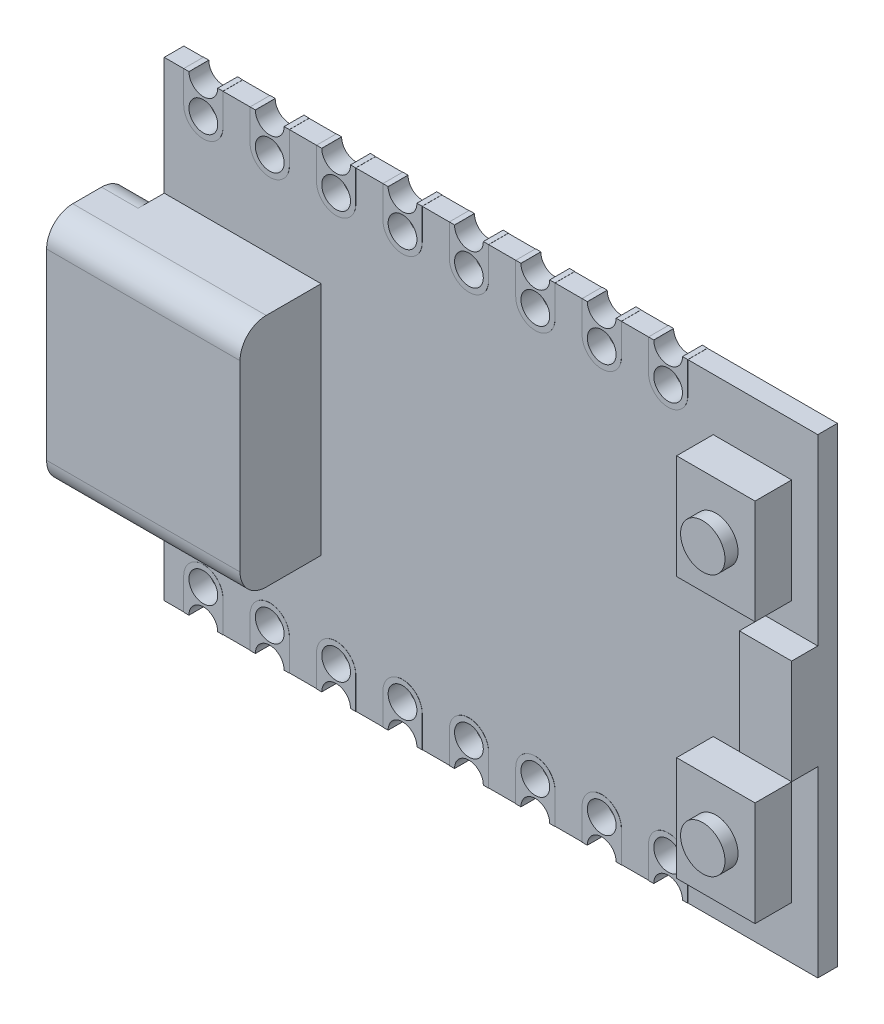
SolidWorks part; units mm, degrees
ref_plane "Plano frontal" through (0, 0, 0) normal (0, 0, 1) x (1, 0, 0)
ref_plane "Plano superior" through (0, 0, 0) normal (0, 1, 0) x (1, 0, 0)
ref_plane "Plano direito" through (0, 0, 0) normal (1, 0, 0) x (0, 0, -1)
sketch "Esboço1" plane through (0, 0, 0) normal (0, 0, 1) x (1, 0, 0)
  line L1 (-25, 18) -> (0, 18)
  line L2 (-25, 18) -> (-25, 0)
  line L3 (-25, 0) -> (0, 0)
  line L4 (0, 18) -> (0, 0)
  dimension "D1" = 18
  dimension "D2" = 25
extrude "PCI" add sketch "Esboço1" along normal blind 0.75
sketch "Esboço2" plane through (0, 0, 0.75) normal (0, 0, 1) x (1, 0, 0)
  line L0 (-15.0711, 10.1145) -> (-11.5355, 13.65)
  line L1 (-15.0711, 10.1145) -> (-11.5355, 6.5789)
  line L2 (-11.5355, 13.65) -> (-8, 10.1145)
  line L3 (-11.5355, 6.5789) -> (-8, 10.1145)
  line L4 (0, 0) -> (0, 18) construction
  line L5 (0, 18) -> (-25, 18) construction
  point P8 (0, 0)
  point P9 (-11.4211, 10.1145)
  point P10 (-11.4211, 10.1145)
  dimension "D1" = 45
  dimension "D2" = 4.35
  dimension "D3" = 8
  dimension "D4" = 5
extrude "ESP32" add sketch "Esboço2" against normal blind 2
sketch "Esboço3" plane through (0, 0, 0.75) normal (0, 0, 1) x (1, 0, 0)
  line L0 (-25, 18) -> (-25, 0) construction
  line L1 (-19, 13.5) -> (-26.4, 13.5)
  line L2 (-19, 13.5) -> (-19, 4.5)
  line L3 (-19, 4.5) -> (-26.4, 4.5)
  line L4 (-26.4, 13.5) -> (-26.4, 4.5)
  line L5 (-25, 9) -> (0, 9) construction
  line L6 (0, 0) -> (0, 18) construction
  dimension "D1" = 1.4
  dimension "D2" = 7.4
  dimension "D3" = 4.5
  dimension "D4" = 9
extrude "USB-C" add sketch "Esboço3" along normal blind 3.1
fillet "Arredondamento inferior USB" radius 1 2 edges at (-25.7, 13.5, 0.75) (-25.7, 4.5, 0.75)
fillet "Arredondamento Superior USB" radius 1 2 edges at (-22.7, 13.5, 3.85) (-22.7, 4.5, 3.85)
sketch "Esboço8" plane through (-26.4, 0, 0) normal (-1, 0, 0) x (0, 0, 1)
  line L0 (1.05, 12.5) -> (1.05, 5.5)
  line L1 (1.75, 4.8) -> (2.85, 4.8)
  line L2 (3.55, 5.5) -> (3.55, 12.5)
  line L3 (2.85, 13.2) -> (1.75, 13.2)
  line L4 (2.85, 13.5) -> (1.75, 13.5) construction
  line L5 (3.85, 12.5) -> (3.85, 5.5) construction
  arc A0 (1.75, 13.2) -> (1.05, 12.5) centre (1.75, 12.5) ccw
  arc A1 (1.05, 5.5) -> (1.75, 4.8) centre (1.75, 5.5) ccw
  arc A2 (2.85, 4.8) -> (3.55, 5.5) centre (2.85, 5.5) ccw
  arc A3 (3.55, 12.5) -> (2.85, 13.2) centre (2.85, 12.5) ccw
  dimension "D1" = 0.7
  dimension "D2" = 0.3
  dimension "D3" = 2.8
  dimension "D4" = 0.3
  dimension "D5" = 8.7
extrude "Furo USB" cut sketch "Esboço8" against normal blind 3.1
sketch "Esboço9" plane through (-26.4, 0, 0) normal (-1, 0, 0) x (0, 0, 1)
  line L0 (2.3, 13.2) -> (2.3, 4.8) construction
  line L1 (2.85, 13.2) -> (1.75, 13.2) construction
  line L2 (1.75, 4.8) -> (2.85, 4.8) construction
  line L3 (1.925, 5.4) -> (2.675, 5.4)
  line L4 (1.925, 5.4) -> (1.925, 12.6)
  line L5 (1.925, 12.6) -> (2.675, 12.6)
  line L6 (2.675, 5.4) -> (2.675, 12.6)
  line L7 (1.925, 5.4) -> (2.675, 12.6) construction
  line L8 (1.925, 12.6) -> (2.675, 5.4) construction
  point P4 (2.3, 9)
  dimension "D1" = 0.6
  dimension "D2" = 0.6
  dimension "D3" = 0.75
extrude "ConexaoUSB" add sketch "Esboço9" against normal up to next from offset 0.5 offset against normal yes
sketch "Esboço10" plane through (0, 0, 0.75) normal (0, 0, 1) x (1, 0, 0)
  line L0 (-25, 0) -> (0, 0) construction
  line L1 (-25, 4.5) -> (-25, 0) construction
  line L2 (-23.5, 1.2) -> (-23.5, -0.7241) construction
  line L3 (-23.5, 16.8) -> (-23.5, 18.7241) construction
  line L4 (0, 9) -> (-28.3512, 9) construction
  line L5 (0, 0) -> (0, 18) construction
  circle A0 centre (-23.5, 1.2) radius 0.55
  circle A1 centre (-23.5, 0) radius 0.55
  circle A2 centre (-20.96, 1.2) radius 0.55
  circle A3 centre (-20.96, 0) radius 0.55
  circle A4 centre (-18.42, 1.2) radius 0.55
  circle A5 centre (-18.42, 0) radius 0.55
  circle A6 centre (-15.88, 1.2) radius 0.55
  circle A7 centre (-15.88, 0) radius 0.55
  circle A8 centre (-13.34, 1.2) radius 0.55
  circle A9 centre (-13.34, 0) radius 0.55
  circle A10 centre (-10.8, 1.2) radius 0.55
  circle A11 centre (-10.8, 0) radius 0.55
  circle A12 centre (-8.26, 1.2) radius 0.55
  circle A13 centre (-8.26, 0) radius 0.55
  circle A14 centre (-5.72, 1.2) radius 0.55
  circle A15 centre (-5.72, 0) radius 0.55
  circle A16 centre (-5.72, 18) radius 0.55
  circle A17 centre (-5.72, 16.8) radius 0.55
  circle A18 centre (-8.26, 18) radius 0.55
  circle A19 centre (-8.26, 16.8) radius 0.55
  circle A20 centre (-10.8, 18) radius 0.55
  circle A21 centre (-10.8, 16.8) radius 0.55
  circle A22 centre (-13.34, 18) radius 0.55
  circle A23 centre (-13.34, 16.8) radius 0.55
  circle A24 centre (-15.88, 18) radius 0.55
  circle A25 centre (-15.88, 16.8) radius 0.55
  circle A26 centre (-18.42, 18) radius 0.55
  circle A27 centre (-18.42, 16.8) radius 0.55
  circle A28 centre (-20.96, 18) radius 0.55
  circle A29 centre (-20.96, 16.8) radius 0.55
  circle A30 centre (-23.5, 18) radius 0.55
  circle A31 centre (-23.5, 16.8) radius 0.55
  dimension "D1" = 1.2
  dimension "D2" = 1.1
  dimension "D7" = 2.54
  dimension "D3" = 0
  dimension "D4" = 1.5
  dimension "D5" = 8
extrude "FurosPCB" cut sketch "Esboço10" against normal up to next (0.75 mm away)
sketch "Esboço11" plane through (0, 0, 0.75) normal (0, 0, 1) x (1, 0, 0)
  line L0 (-24.25, 1.2) -> (-24.25, 0)
  line L1 (-22.75, 1.2) -> (-22.75, 0)
  line L2 (-20.21, 1.2) -> (-20.21, 0)
  line L4 (-24.25, 0) -> (-24.05, 0)
  line L5 (-22.95, 0) -> (-22.75, 0)
  line L6 (-20.41, 0) -> (-20.21, 0)
  line L7 (-21.71, 1.2) -> (-21.71, 0)
  line L8 (-21.71, 0) -> (-21.51, 0)
  line L9 (-17.67, 1.2) -> (-17.67, 0)
  line L10 (-17.87, 0) -> (-17.67, 0)
  line L11 (-19.17, 1.2) -> (-19.17, 0)
  line L12 (-19.17, 0) -> (-18.97, 0)
  line L13 (-15.13, 1.2) -> (-15.13, 0)
  line L14 (-15.33, 0) -> (-15.13, 0)
  line L15 (-16.63, 1.2) -> (-16.63, 0)
  line L16 (-16.63, 0) -> (-16.43, 0)
  line L17 (-12.59, 1.2) -> (-12.59, 0)
  line L18 (-12.79, 0) -> (-12.59, 0)
  line L19 (-14.09, 1.2) -> (-14.09, 0)
  line L20 (-14.09, 0) -> (-13.89, 0)
  line L21 (-10.05, 1.2) -> (-10.05, 0)
  line L22 (-10.25, 0) -> (-10.05, 0)
  line L23 (-11.55, 1.2) -> (-11.55, 0)
  line L24 (-11.55, 0) -> (-11.35, 0)
  line L25 (-7.51, 1.2) -> (-7.51, 0)
  line L26 (-7.71, 0) -> (-7.51, 0)
  line L27 (-9.01, 1.2) -> (-9.01, 0)
  line L28 (-9.01, 0) -> (-8.81, 0)
  line L29 (-4.97, 1.2) -> (-4.97, 0)
  line L30 (-5.17, 0) -> (-4.97, 0)
  line L31 (-6.47, 1.2) -> (-6.47, 0)
  line L32 (-6.47, 0) -> (-6.27, 0)
  line L33 (0, 9) -> (-27.4378, 9) construction
  line L34 (0, 0) -> (0, 18) construction
  line L35 (-6.47, 18) -> (-6.27, 18)
  line L36 (-6.47, 16.8) -> (-6.47, 18)
  line L37 (-5.17, 18) -> (-4.97, 18)
  line L38 (-4.97, 16.8) -> (-4.97, 18)
  line L39 (-9.01, 18) -> (-8.81, 18)
  line L40 (-9.01, 16.8) -> (-9.01, 18)
  line L41 (-7.71, 18) -> (-7.51, 18)
  line L42 (-7.51, 16.8) -> (-7.51, 18)
  line L43 (-11.55, 18) -> (-11.35, 18)
  line L44 (-11.55, 16.8) -> (-11.55, 18)
  line L45 (-10.25, 18) -> (-10.05, 18)
  line L46 (-10.05, 16.8) -> (-10.05, 18)
  line L47 (-14.09, 18) -> (-13.89, 18)
  line L48 (-14.09, 16.8) -> (-14.09, 18)
  line L49 (-12.79, 18) -> (-12.59, 18)
  line L50 (-12.59, 16.8) -> (-12.59, 18)
  line L51 (-16.63, 18) -> (-16.43, 18)
  line L52 (-16.63, 16.8) -> (-16.63, 18)
  line L53 (-15.33, 18) -> (-15.13, 18)
  line L54 (-15.13, 16.8) -> (-15.13, 18)
  line L55 (-19.17, 18) -> (-18.97, 18)
  line L56 (-19.17, 16.8) -> (-19.17, 18)
  line L57 (-17.87, 18) -> (-17.67, 18)
  line L58 (-17.67, 16.8) -> (-17.67, 18)
  line L59 (-21.71, 18) -> (-21.51, 18)
  line L60 (-21.71, 16.8) -> (-21.71, 18)
  line L61 (-20.41, 18) -> (-20.21, 18)
  line L62 (-22.95, 18) -> (-22.75, 18)
  line L63 (-24.25, 18) -> (-24.05, 18)
  line L64 (-20.21, 16.8) -> (-20.21, 18)
  line L65 (-22.75, 16.8) -> (-22.75, 18)
  line L66 (-24.25, 16.8) -> (-24.25, 18)
  arc A9 (-22.95, 0) -> (-24.05, 0) centre (-23.5, 0) ccw construction
  circle A10 centre (-23.5, 1.2) radius 0.75
  arc A11 (-22.75, 1.2) -> (-24.25, 1.2) centre (-23.5, 1.2) ccw
  arc A12 (-22.95, 0) -> (-24.05, 0) centre (-23.5, 0) ccw
  circle A13 centre (-23.5, 1.2) radius 0.55 construction
  circle A14 centre (-23.5, 1.2) radius 0.55
  arc A15 (-20.41, 0) -> (-21.51, 0) centre (-20.96, 0) ccw
  circle A16 centre (-20.96, 1.2) radius 0.55
  arc A17 (-20.21, 1.2) -> (-21.71, 1.2) centre (-20.96, 1.2) ccw
  arc A18 (-17.87, 0) -> (-18.97, 0) centre (-18.42, 0) ccw
  circle A19 centre (-18.42, 1.2) radius 0.55
  arc A20 (-17.67, 1.2) -> (-19.17, 1.2) centre (-18.42, 1.2) ccw
  arc A21 (-15.33, 0) -> (-16.43, 0) centre (-15.88, 0) ccw
  circle A22 centre (-15.88, 1.2) radius 0.55
  arc A23 (-15.13, 1.2) -> (-16.63, 1.2) centre (-15.88, 1.2) ccw
  arc A24 (-12.79, 0) -> (-13.89, 0) centre (-13.34, 0) ccw
  circle A25 centre (-13.34, 1.2) radius 0.55
  arc A26 (-12.59, 1.2) -> (-14.09, 1.2) centre (-13.34, 1.2) ccw
  arc A27 (-10.25, 0) -> (-11.35, 0) centre (-10.8, 0) ccw
  circle A28 centre (-10.8, 1.2) radius 0.55
  arc A29 (-10.05, 1.2) -> (-11.55, 1.2) centre (-10.8, 1.2) ccw
  arc A30 (-7.71, 0) -> (-8.81, 0) centre (-8.26, 0) ccw
  circle A31 centre (-8.26, 1.2) radius 0.55
  arc A32 (-7.51, 1.2) -> (-9.01, 1.2) centre (-8.26, 1.2) ccw
  arc A33 (-5.17, 0) -> (-6.27, 0) centre (-5.72, 0) ccw
  circle A34 centre (-5.72, 1.2) radius 0.55
  arc A35 (-4.97, 1.2) -> (-6.47, 1.2) centre (-5.72, 1.2) ccw
  arc A36 (-4.97, 16.8) -> (-6.47, 16.8) centre (-5.72, 16.8) cw
  circle A37 centre (-5.72, 16.8) radius 0.55
  arc A38 (-5.17, 18) -> (-6.27, 18) centre (-5.72, 18) cw
  arc A39 (-7.51, 16.8) -> (-9.01, 16.8) centre (-8.26, 16.8) cw
  circle A40 centre (-8.26, 16.8) radius 0.55
  arc A41 (-7.71, 18) -> (-8.81, 18) centre (-8.26, 18) cw
  arc A42 (-10.05, 16.8) -> (-11.55, 16.8) centre (-10.8, 16.8) cw
  circle A43 centre (-10.8, 16.8) radius 0.55
  arc A44 (-10.25, 18) -> (-11.35, 18) centre (-10.8, 18) cw
  arc A45 (-12.59, 16.8) -> (-14.09, 16.8) centre (-13.34, 16.8) cw
  circle A46 centre (-13.34, 16.8) radius 0.55
  arc A47 (-12.79, 18) -> (-13.89, 18) centre (-13.34, 18) cw
  arc A48 (-15.13, 16.8) -> (-16.63, 16.8) centre (-15.88, 16.8) cw
  circle A49 centre (-15.88, 16.8) radius 0.55
  arc A50 (-15.33, 18) -> (-16.43, 18) centre (-15.88, 18) cw
  arc A51 (-17.67, 16.8) -> (-19.17, 16.8) centre (-18.42, 16.8) cw
  circle A52 centre (-18.42, 16.8) radius 0.55
  arc A53 (-17.87, 18) -> (-18.97, 18) centre (-18.42, 18) cw
  arc A54 (-20.21, 16.8) -> (-21.71, 16.8) centre (-20.96, 16.8) cw
  circle A55 centre (-20.96, 16.8) radius 0.55
  arc A56 (-20.41, 18) -> (-21.51, 18) centre (-20.96, 18) cw
  circle A57 centre (-23.5, 16.8) radius 0.55
  arc A58 (-22.95, 18) -> (-24.05, 18) centre (-23.5, 18) cw
  arc A59 (-22.75, 16.8) -> (-24.25, 16.8) centre (-23.5, 16.8) cw
  dimension "D1" = 0.2
  dimension "D2" = 8
extrude "PADs" add sketch "Esboço11" along normal blind 0.005
sketch "Esboço13" plane through (0, 0, 0) normal (0, 0, -1) x (-1, 0, 0)
  line L0 (25, 0) -> (24.05, 0) construction
  line L1 (22.95, 0) -> (21.51, 0) construction
  line L2 (24.25, 0) -> (24.05, 0)
  line L3 (22.95, 0) -> (22.75, 0)
  line L4 (22.75, 1.2) -> (22.75, 0)
  line L5 (24.25, 1.2) -> (24.25, 0)
  line L6 (21.71, 1.2) -> (21.71, 0)
  line L7 (21.71, 0) -> (21.51, 0)
  line L8 (20.41, 0) -> (20.21, 0)
  line L9 (20.21, 1.2) -> (20.21, 0)
  line L10 (19.17, 1.2) -> (19.17, 0)
  line L11 (19.17, 0) -> (18.97, 0)
  line L12 (17.87, 0) -> (17.67, 0)
  line L13 (17.67, 1.2) -> (17.67, 0)
  line L14 (16.63, 1.2) -> (16.63, 0)
  line L15 (16.63, 0) -> (16.43, 0)
  line L16 (15.33, 0) -> (15.13, 0)
  line L17 (15.13, 1.2) -> (15.13, 0)
  line L18 (14.09, 1.2) -> (14.09, 0)
  line L19 (14.09, 0) -> (13.89, 0)
  line L20 (12.79, 0) -> (12.59, 0)
  line L21 (12.59, 1.2) -> (12.59, 0)
  line L22 (11.55, 1.2) -> (11.55, 0)
  line L23 (11.55, 0) -> (11.35, 0)
  line L24 (10.25, 0) -> (10.05, 0)
  line L25 (10.05, 1.2) -> (10.05, 0)
  line L26 (9.01, 1.2) -> (9.01, 0)
  line L27 (9.01, 0) -> (8.81, 0)
  line L28 (7.71, 0) -> (7.51, 0)
  line L29 (7.51, 1.2) -> (7.51, 0)
  line L30 (6.47, 1.2) -> (6.47, 0)
  line L31 (6.47, 0) -> (6.27, 0)
  line L32 (5.17, 0) -> (4.97, 0)
  line L33 (4.97, 1.2) -> (4.97, 0)
  line L34 (0, 9) -> (25, 9) construction
  line L35 (0, 0) -> (0, 18) construction
  line L36 (25, 18) -> (25, 0) construction
  line L37 (4.97, 16.8) -> (4.97, 18)
  line L38 (5.17, 18) -> (4.97, 18)
  line L39 (6.47, 18) -> (6.27, 18)
  line L40 (6.47, 16.8) -> (6.47, 18)
  line L41 (7.51, 16.8) -> (7.51, 18)
  line L42 (7.71, 18) -> (7.51, 18)
  line L43 (9.01, 18) -> (8.81, 18)
  line L44 (9.01, 16.8) -> (9.01, 18)
  line L45 (10.05, 16.8) -> (10.05, 18)
  line L46 (10.25, 18) -> (10.05, 18)
  line L47 (11.55, 18) -> (11.35, 18)
  line L48 (11.55, 16.8) -> (11.55, 18)
  line L49 (12.59, 16.8) -> (12.59, 18)
  line L50 (12.79, 18) -> (12.59, 18)
  line L51 (14.09, 18) -> (13.89, 18)
  line L52 (14.09, 16.8) -> (14.09, 18)
  line L53 (15.13, 16.8) -> (15.13, 18)
  line L54 (15.33, 18) -> (15.13, 18)
  line L55 (16.63, 18) -> (16.43, 18)
  line L56 (16.63, 16.8) -> (16.63, 18)
  line L57 (17.67, 16.8) -> (17.67, 18)
  line L58 (17.87, 18) -> (17.67, 18)
  line L59 (19.17, 18) -> (18.97, 18)
  line L60 (19.17, 16.8) -> (19.17, 18)
  line L61 (20.21, 16.8) -> (20.21, 18)
  line L62 (20.41, 18) -> (20.21, 18)
  line L63 (21.71, 18) -> (21.51, 18)
  line L64 (21.71, 16.8) -> (21.71, 18)
  line L65 (24.25, 16.8) -> (24.25, 18)
  line L66 (22.75, 16.8) -> (22.75, 18)
  line L67 (22.95, 18) -> (22.75, 18)
  line L68 (24.25, 18) -> (24.05, 18)
  circle A0 centre (23.5, 1.2) radius 0.55 construction
  arc A1 (24.05, 0) -> (22.95, 0) centre (23.5, 0) ccw construction
  circle A2 centre (23.5, 1.2) radius 0.55
  arc A3 (24.05, 0) -> (22.95, 0) centre (23.5, 0) ccw
  arc A4 (24.25, 1.2) -> (22.75, 1.2) centre (23.5, 1.2) ccw
  circle A5 centre (23.5, 1.2) radius 0.75 construction
  arc A6 (21.51, 0) -> (20.41, 0) centre (20.96, 0) ccw
  arc A7 (21.71, 1.2) -> (20.21, 1.2) centre (20.96, 1.2) ccw
  circle A8 centre (20.96, 1.2) radius 0.55
  arc A9 (18.97, 0) -> (17.87, 0) centre (18.42, 0) ccw
  arc A10 (19.17, 1.2) -> (17.67, 1.2) centre (18.42, 1.2) ccw
  circle A11 centre (18.42, 1.2) radius 0.55
  arc A12 (16.43, 0) -> (15.33, 0) centre (15.88, 0) ccw
  arc A13 (16.63, 1.2) -> (15.13, 1.2) centre (15.88, 1.2) ccw
  circle A14 centre (15.88, 1.2) radius 0.55
  arc A15 (13.89, 0) -> (12.79, 0) centre (13.34, 0) ccw
  arc A16 (14.09, 1.2) -> (12.59, 1.2) centre (13.34, 1.2) ccw
  circle A17 centre (13.34, 1.2) radius 0.55
  arc A18 (11.35, 0) -> (10.25, 0) centre (10.8, 0) ccw
  arc A19 (11.55, 1.2) -> (10.05, 1.2) centre (10.8, 1.2) ccw
  circle A20 centre (10.8, 1.2) radius 0.55
  arc A21 (8.81, 0) -> (7.71, 0) centre (8.26, 0) ccw
  arc A22 (9.01, 1.2) -> (7.51, 1.2) centre (8.26, 1.2) ccw
  circle A23 centre (8.26, 1.2) radius 0.55
  arc A24 (6.27, 0) -> (5.17, 0) centre (5.72, 0) ccw
  arc A25 (6.47, 1.2) -> (4.97, 1.2) centre (5.72, 1.2) ccw
  circle A26 centre (5.72, 1.2) radius 0.55
  circle A27 centre (5.72, 16.8) radius 0.55
  arc A28 (6.47, 16.8) -> (4.97, 16.8) centre (5.72, 16.8) cw
  arc A29 (6.27, 18) -> (5.17, 18) centre (5.72, 18) cw
  circle A30 centre (8.26, 16.8) radius 0.55
  arc A31 (9.01, 16.8) -> (7.51, 16.8) centre (8.26, 16.8) cw
  arc A32 (8.81, 18) -> (7.71, 18) centre (8.26, 18) cw
  circle A33 centre (10.8, 16.8) radius 0.55
  arc A34 (11.55, 16.8) -> (10.05, 16.8) centre (10.8, 16.8) cw
  arc A35 (11.35, 18) -> (10.25, 18) centre (10.8, 18) cw
  circle A36 centre (13.34, 16.8) radius 0.55
  arc A37 (14.09, 16.8) -> (12.59, 16.8) centre (13.34, 16.8) cw
  arc A38 (13.89, 18) -> (12.79, 18) centre (13.34, 18) cw
  circle A39 centre (15.88, 16.8) radius 0.55
  arc A40 (16.63, 16.8) -> (15.13, 16.8) centre (15.88, 16.8) cw
  arc A41 (16.43, 18) -> (15.33, 18) centre (15.88, 18) cw
  circle A42 centre (18.42, 16.8) radius 0.55
  arc A43 (19.17, 16.8) -> (17.67, 16.8) centre (18.42, 16.8) cw
  arc A44 (18.97, 18) -> (17.87, 18) centre (18.42, 18) cw
  circle A45 centre (20.96, 16.8) radius 0.55
  arc A46 (21.71, 16.8) -> (20.21, 16.8) centre (20.96, 16.8) cw
  arc A47 (21.51, 18) -> (20.41, 18) centre (20.96, 18) cw
  arc A48 (24.25, 16.8) -> (22.75, 16.8) centre (23.5, 16.8) cw
  arc A49 (24.05, 18) -> (22.95, 18) centre (23.5, 18) cw
  circle A50 centre (23.5, 16.8) radius 0.55
  dimension "D1" = 0.2
  dimension "D2" = 8
extrude "InferiorPads" add sketch "Esboço13" along normal blind 0.005
sketch "Esboço14" plane through (0, 18, 0) normal (0, 1, 0) x (1, 0, 0)
  line L0 (-24.25, 0.005) -> (-24.25, -0.755)
  line L1 (-24.25, -0.755) -> (-24.05, -0.755)
  line L2 (-24.05, -0.755) -> (-24.05, 0.005)
  line L3 (-24.05, 0.005) -> (-24.25, 0.005)
  line L4 (-22.95, 0.005) -> (-22.75, 0)
  line L5 (-22.75, 0) -> (-22.75, -0.755)
  line L6 (-22.75, -0.755) -> (-22.95, -0.755)
  line L7 (-22.95, -0.755) -> (-22.95, 0.005)
  line L8 (-21.71, 0.005) -> (-21.71, -0.755)
  line L9 (-21.51, 0.005) -> (-21.71, 0.005)
  line L10 (-21.51, -0.755) -> (-21.51, 0.005)
  line L11 (-21.71, -0.755) -> (-21.51, -0.755)
  line L12 (-20.41, -0.755) -> (-20.41, 0.005)
  line L13 (-20.41, 0.005) -> (-20.21, 0)
  line L14 (-20.21, 0) -> (-20.21, -0.755)
  line L15 (-20.21, -0.755) -> (-20.41, -0.755)
  line L16 (-19.17, 0.005) -> (-19.17, -0.755)
  line L17 (-18.97, 0.005) -> (-19.17, 0.005)
  line L18 (-18.97, -0.755) -> (-18.97, 0.005)
  line L19 (-19.17, -0.755) -> (-18.97, -0.755)
  line L20 (-17.87, -0.755) -> (-17.87, 0.005)
  line L21 (-17.87, 0.005) -> (-17.67, 0)
  line L22 (-17.67, 0) -> (-17.67, -0.755)
  line L23 (-17.67, -0.755) -> (-17.87, -0.755)
  line L24 (-16.63, 0.005) -> (-16.63, -0.755)
  line L25 (-16.43, 0.005) -> (-16.63, 0.005)
  line L26 (-16.43, -0.755) -> (-16.43, 0.005)
  line L27 (-16.63, -0.755) -> (-16.43, -0.755)
  line L28 (-15.33, -0.755) -> (-15.33, 0.005)
  line L29 (-15.33, 0.005) -> (-15.13, 0)
  line L30 (-15.13, 0) -> (-15.13, -0.755)
  line L31 (-15.13, -0.755) -> (-15.33, -0.755)
  line L32 (-14.09, 0.005) -> (-14.09, -0.755)
  line L33 (-13.89, 0.005) -> (-14.09, 0.005)
  line L34 (-13.89, -0.755) -> (-13.89, 0.005)
  line L35 (-14.09, -0.755) -> (-13.89, -0.755)
  line L36 (-12.79, -0.755) -> (-12.79, 0.005)
  line L37 (-12.79, 0.005) -> (-12.59, 0)
  line L38 (-12.59, 0) -> (-12.59, -0.755)
  line L39 (-12.59, -0.755) -> (-12.79, -0.755)
  line L40 (-11.55, 0.005) -> (-11.55, -0.755)
  line L41 (-11.35, 0.005) -> (-11.55, 0.005)
  line L42 (-11.35, -0.755) -> (-11.35, 0.005)
  line L43 (-11.55, -0.755) -> (-11.35, -0.755)
  line L44 (-10.25, -0.755) -> (-10.25, 0.005)
  line L45 (-10.25, 0.005) -> (-10.05, 0)
  line L46 (-10.05, 0) -> (-10.05, -0.755)
  line L47 (-10.05, -0.755) -> (-10.25, -0.755)
  line L48 (-9.01, 0.005) -> (-9.01, -0.755)
  line L49 (-8.81, 0.005) -> (-9.01, 0.005)
  line L50 (-8.81, -0.755) -> (-8.81, 0.005)
  line L51 (-9.01, -0.755) -> (-8.81, -0.755)
  line L52 (-7.71, -0.755) -> (-7.71, 0.005)
  line L53 (-7.71, 0.005) -> (-7.51, 0)
  line L54 (-7.51, 0) -> (-7.51, -0.755)
  line L55 (-7.51, -0.755) -> (-7.71, -0.755)
  line L56 (-6.47, 0.005) -> (-6.47, -0.755)
  line L57 (-6.27, 0.005) -> (-6.47, 0.005)
  line L58 (-6.27, -0.755) -> (-6.27, 0.005)
  line L59 (-6.47, -0.755) -> (-6.27, -0.755)
  line L60 (-5.17, -0.755) -> (-5.17, 0.005)
  line L61 (-5.17, 0.005) -> (-4.97, 0)
  line L62 (-4.97, 0) -> (-4.97, -0.755)
  line L63 (-4.97, -0.755) -> (-5.17, -0.755)
  dimension "D1" = 8
extrude "PADEx" add sketch "Esboço14" along normal blind 0.005
sketch "Esboço16" plane through (0, 0, 0) normal (0, -1, 0) x (1, 0, 0)
  line L0 (-24.25, 0.755) -> (-24.05, 0.755) construction
  line L1 (-24.25, 0.755) -> (-24.05, 0.755)
  line L2 (-24.25, 0.755) -> (-24.25, -0.005)
  line L3 (-24.25, -0.005) -> (-24.05, -0.005)
  line L4 (-24.05, 0.755) -> (-24.05, -0.005)
  line L5 (-22.95, -0.005) -> (-22.75, -0.005)
  line L6 (-22.95, -0.005) -> (-22.95, 0.755)
  line L7 (-22.95, 0.755) -> (-22.75, 0.755)
  line L8 (-22.75, -0.005) -> (-22.75, 0.755)
  line L9 (-24.25, 0.755) -> (-24.25, 0.75) construction
  line L10 (-20.21, -0.005) -> (-20.21, 0.755)
  line L11 (-20.41, -0.005) -> (-20.41, 0.755)
  line L12 (-20.41, -0.005) -> (-20.21, -0.005)
  line L13 (-20.41, 0.755) -> (-20.21, 0.755)
  line L14 (-21.71, 0.755) -> (-21.51, 0.755)
  line L15 (-21.71, 0.755) -> (-21.71, -0.005)
  line L16 (-21.71, -0.005) -> (-21.51, -0.005)
  line L17 (-21.51, 0.755) -> (-21.51, -0.005)
  line L18 (-17.67, -0.005) -> (-17.67, 0.755)
  line L19 (-17.87, -0.005) -> (-17.87, 0.755)
  line L20 (-17.87, -0.005) -> (-17.67, -0.005)
  line L21 (-17.87, 0.755) -> (-17.67, 0.755)
  line L22 (-19.17, 0.755) -> (-18.97, 0.755)
  line L23 (-19.17, 0.755) -> (-19.17, -0.005)
  line L24 (-19.17, -0.005) -> (-18.97, -0.005)
  line L25 (-18.97, 0.755) -> (-18.97, -0.005)
  line L26 (-15.13, -0.005) -> (-15.13, 0.755)
  line L27 (-15.33, -0.005) -> (-15.33, 0.755)
  line L28 (-15.33, -0.005) -> (-15.13, -0.005)
  line L29 (-15.33, 0.755) -> (-15.13, 0.755)
  line L30 (-16.63, 0.755) -> (-16.43, 0.755)
  line L31 (-16.63, 0.755) -> (-16.63, -0.005)
  line L32 (-16.63, -0.005) -> (-16.43, -0.005)
  line L33 (-16.43, 0.755) -> (-16.43, -0.005)
  line L34 (-12.59, -0.005) -> (-12.59, 0.755)
  line L35 (-12.79, -0.005) -> (-12.79, 0.755)
  line L36 (-12.79, -0.005) -> (-12.59, -0.005)
  line L37 (-12.79, 0.755) -> (-12.59, 0.755)
  line L38 (-14.09, 0.755) -> (-13.89, 0.755)
  line L39 (-14.09, 0.755) -> (-14.09, -0.005)
  line L40 (-14.09, -0.005) -> (-13.89, -0.005)
  line L41 (-13.89, 0.755) -> (-13.89, -0.005)
  line L42 (-10.05, -0.005) -> (-10.05, 0.755)
  line L43 (-10.25, -0.005) -> (-10.25, 0.755)
  line L44 (-10.25, -0.005) -> (-10.05, -0.005)
  line L45 (-10.25, 0.755) -> (-10.05, 0.755)
  line L46 (-11.55, 0.755) -> (-11.35, 0.755)
  line L47 (-11.55, 0.755) -> (-11.55, -0.005)
  line L48 (-11.55, -0.005) -> (-11.35, -0.005)
  line L49 (-11.35, 0.755) -> (-11.35, -0.005)
  line L50 (-7.51, -0.005) -> (-7.51, 0.755)
  line L51 (-7.71, -0.005) -> (-7.71, 0.755)
  line L52 (-7.71, -0.005) -> (-7.51, -0.005)
  line L53 (-7.71, 0.755) -> (-7.51, 0.755)
  line L54 (-9.01, 0.755) -> (-8.81, 0.755)
  line L55 (-9.01, 0.755) -> (-9.01, -0.005)
  line L56 (-9.01, -0.005) -> (-8.81, -0.005)
  line L57 (-8.81, 0.755) -> (-8.81, -0.005)
  line L58 (-4.97, -0.005) -> (-4.97, 0.755)
  line L59 (-5.17, -0.005) -> (-5.17, 0.755)
  line L60 (-5.17, -0.005) -> (-4.97, -0.005)
  line L61 (-5.17, 0.755) -> (-4.97, 0.755)
  line L62 (-6.47, 0.755) -> (-6.27, 0.755)
  line L63 (-6.47, 0.755) -> (-6.47, -0.005)
  line L64 (-6.47, -0.005) -> (-6.27, -0.005)
  line L65 (-6.27, 0.755) -> (-6.27, -0.005)
  dimension "D1" = 8
extrude "PADEx1" add sketch "Esboço16" along normal blind 0.005
sketch "Esboço17" plane through (0, 0, 0.75) normal (0, 0, 1) x (1, 0, 0)
  line L0 (0, 18) -> (-4.97, 18) construction
  line L1 (-2, 11) -> (0, 11)
  line L2 (-2, 11) -> (-2, 7)
  line L3 (-2, 7) -> (0, 7)
  line L4 (0, 11) -> (0, 7)
  line L5 (0, 0) -> (0, 18) construction
  dimension "D1" = 7
  dimension "D2" = 4
  dimension "D3" = 2
extrude "Antena" add sketch "Esboço17" along normal blind 1
sketch "Esboço18" plane through (0, 0, 0.75) normal (0, 0, 1) x (1, 0, 0)
  line L0 (-19, 4.5) -> (-19, 13.5) construction
  line L1 (-4, 16) -> (-1, 16)
  line L2 (-4, 16) -> (-4, 12)
  line L3 (-4, 12) -> (-1, 12)
  line L4 (-1, 16) -> (-1, 12)
  line L5 (-4, 6) -> (-1, 6)
  line L6 (-4, 6) -> (-4, 2)
  line L7 (-4, 2) -> (-1, 2)
  line L8 (-1, 6) -> (-1, 2)
  line L9 (-16.63, 18) -> (-17.67, 18) construction
  point P8 (-19, 9)
  dimension "D1" = 4
  dimension "D2" = 3
  dimension "D3" = 15
  dimension "D4" = 6
  dimension "D5" = 6
extrude "Buttons" add sketch "Esboço18" along normal blind 1.4
sketch "Esboço19" plane through (0, 0, 2.15) normal (0, 0, 1) x (1, 0, 0)
  line L0 (-1, 12) -> (-1, 16) construction
  line L2 (-1, 16) -> (-4, 16) construction
  line L4 (-1, 6) -> (-4, 6) construction
  line L5 (-1, 2) -> (-1, 6) construction
  circle A0 centre (-2.5, 4) radius 0.85
  circle A1 centre (-2.5, 14) radius 0.85
  dimension "D1" = 1.7
  dimension "D2" = 1.5
  dimension "D3" = 2
  dimension "D4" = 2
  dimension "D5" = 1.5
extrude "Ressalto-extrusão12" add sketch "Esboço19" along normal blind 0.5
sketch "Esboço20" plane through (0, 0, 0.75) normal (0, 0, 1) x (1, 0, 0)
  line L0 (-7.51, 0) -> (-6.47, 0) construction
  line L1 (-5.5, 6.4) -> (-3, 6.4)
  line L2 (-5.5, 6.4) -> (-5.5, 3.4)
  line L3 (-5.5, 3.4) -> (-3, 3.4)
  line L4 (-3, 6.4) -> (-3, 3.4)
  line L5 (0, 0) -> (0, 7) construction
  dimension "D1" = 3
  dimension "D2" = 2.5
  dimension "D3" = 3.4
  dimension "D4" = 3
extrude "Ressalto-extrusão13" add sketch "Esboço20" against normal blind 1.7
chamfer "Chanfro1" distance 0.2 angle 45 4 edges at (-4.25, 6.4, -0.95) (-3, 4.9, -0.95) (-4.25, 3.4, -0.95) (-5.5, 4.9, -0.95)
